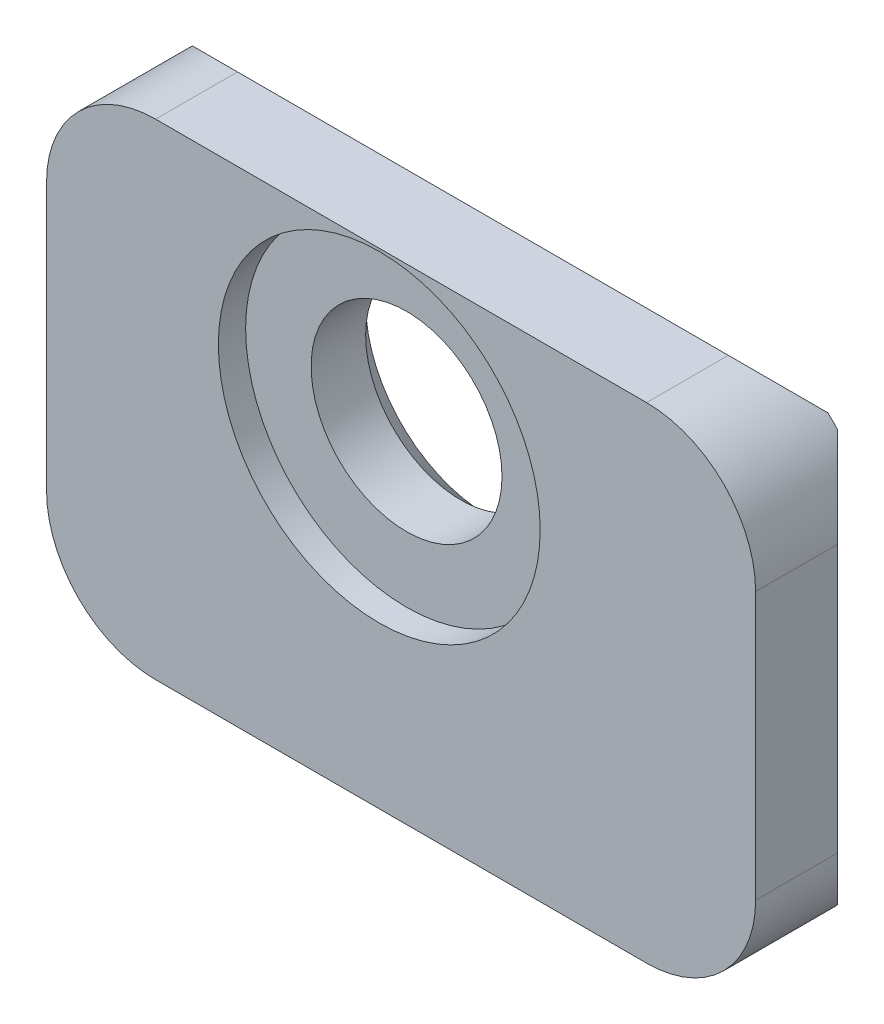
SolidWorks part; units mm, degrees
material "ABS"
ref_plane "Top Plane" through (0, 0, 0) normal (0, 0, 1) x (1, 0, 0)
ref_plane "Front Plane" through (0, 0, 0) normal (0, 1, 0) x (1, 0, 0)
ref_plane "Right Plane" through (0, 0, 0) normal (1, 0, 0) x (0, 0, -1)
sketch "Sketch1" plane through (0, 0, 0) normal (0, 0, 1) x (1, 0, 0)
  line L1 (-6.5, -4.45) -> (6.5, -4.45)
  line L2 (-6.5, -4.45) -> (-6.5, 4.45)
  line L3 (-6.5, 4.45) -> (6.5, 4.45)
  line L4 (6.5, -4.45) -> (6.5, 4.45)
  line L5 (-6.5, -4.45) -> (6.5, 4.45) construction
  line L6 (-6.5, 4.45) -> (6.5, -4.45) construction
  point P0 (0, 0)
  dimension "D1" = 13
  dimension "D2" = 8.9
extrude "Boss-Extrude1" add sketch "Sketch1" along normal blind 2
sketch "Sketch2" plane through (0, 0, 2) normal (0, 0, 1) x (1, 0, 0)
  line L0 (6.5, 4.45) -> (-6.5, 4.45) construction
  line L1 (-6.5, 4.45) -> (-6.5, -4.45) construction
  circle A0 centre (-0.4, 1.45) radius 1.75
  dimension "D3" = 3.5
  dimension "D1" = 3
  dimension "D2" = 6.1
extrude "Cut-Extrude4" cut sketch "Sketch2" against normal through all
sketch "Sketch3" plane through (0, 0, 2) normal (0, 0, 1) x (1, 0, 0)
  circle A0 centre (-0.4, 1.45) radius 2.95
  dimension "D1" = 5.9
extrude "Cut-Extrude9" cut sketch "Sketch3" against normal blind 0.5
chamfer "Chamfer1" distance 0.5 angle 45 5 edges at (0, 4.45, 0) (-6.5, 0, 0) (0, -4.45, 0) (6.5, 0, 0) (1.35, 1.45, 0)
fillet "Fillet2" radius 2 4 edges at (-6.5, 4.45, 1.25) (6.5, 4.45, 1.25) (6.5, -4.45, 1.25) (-6.5, -4.45, 1.25)
